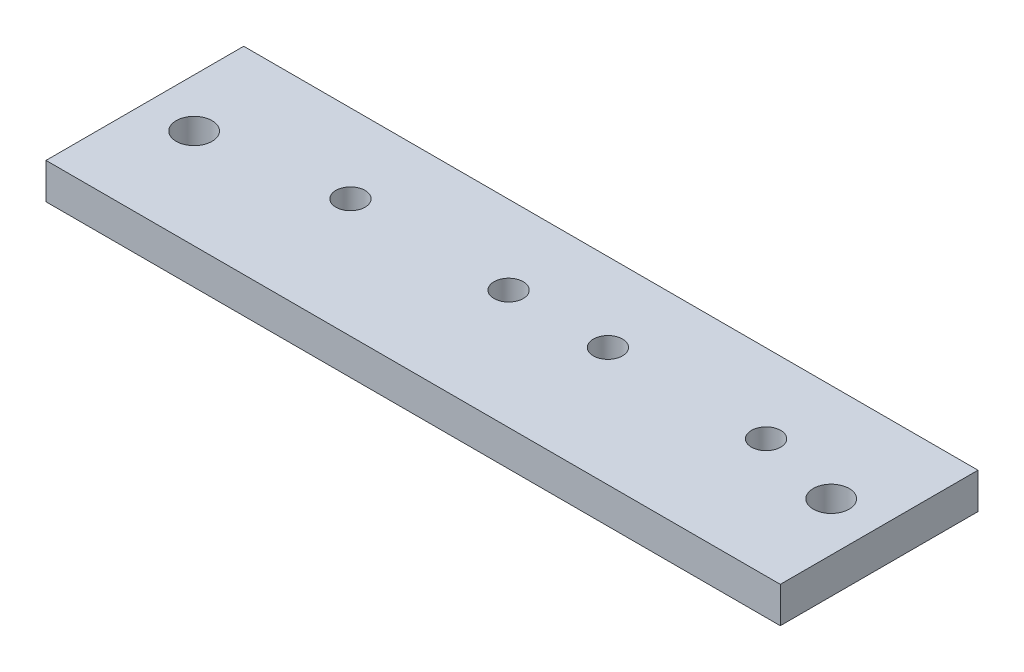
SolidWorks part; units mm, degrees
material "Alumina"
ref_plane "Front Plane" through (0, 0, 0) normal (0, 0, 1) x (1, 0, 0)
ref_plane "Top Plane" through (0, 0, 0) normal (0, 1, 0) x (1, 0, 0)
ref_plane "Right Plane" through (0, 0, 0) normal (1, 0, 0) x (0, 0, -1)
sketch "Sketch1" plane through (0, 0, 0) normal (0, 1, 0) x (1, 0, 0)
  line L1 (0, 0) -> (130, 0)
  line L2 (0, 0) -> (0, -35)
  line L3 (0, -35) -> (130, -35)
  line L4 (130, 0) -> (130, -35)
  dimension "D1" = 130
  dimension "D2" = 35
extrude "Boss-Extrude1" add sketch "Sketch1" along normal blind 6.35
sketch "Sketch5" plane through (0, 6.35, 0) normal (0, 1, 0) x (1, 0, 0)
  line L1 (0, 0) -> (0, -35) construction
  line L2 (130, -35) -> (130, 0) construction
  circle A0 centre (8.605, -17.3826) radius 3.18
  circle A2 centre (121.395, -17.3826) radius 3.18
  dimension "D1" = 8.605
  dimension "D2" = 8.605
extrude "Cut-Extrude2" cut sketch "Sketch5" against normal through all
sketch "Sketch8" plane through (0, 0, 0) normal (0, -1, 0) x (1, 0, 0)
  circle A0 centre (106.4228, 13.9406) radius 2.5866 construction
  circle A1 centre (106.4228, -7.0594) radius 2.5866 construction
  circle A2 centre (78.4228, -7.0594) radius 2.5866 construction
  circle A3 centre (78.4228, 13.9406) radius 2.5866 construction
  circle A4 centre (60.8409, 13.9406) radius 2.5866 construction
  circle A5 centre (60.8409, -7.0594) radius 2.5866 construction
  circle A6 centre (32.8409, -7.0594) radius 2.5866 construction
  circle A7 centre (32.8409, 13.9406) radius 2.5866 construction
  circle A8 centre (106.4228, 13.9406) radius 2.5866
  circle A9 centre (106.4228, -7.0594) radius 2.5866
  circle A10 centre (78.4228, -7.0594) radius 2.5866
  circle A11 centre (78.4228, 13.9406) radius 2.5866
  circle A12 centre (60.8409, 13.9406) radius 2.5866
  circle A13 centre (60.8409, -7.0594) radius 2.5866
  circle A14 centre (32.8409, -7.0594) radius 2.5866
  circle A15 centre (32.8409, 13.9406) radius 2.5866
extrude "Cut-Extrude4" cut sketch "Sketch8" against normal through all
